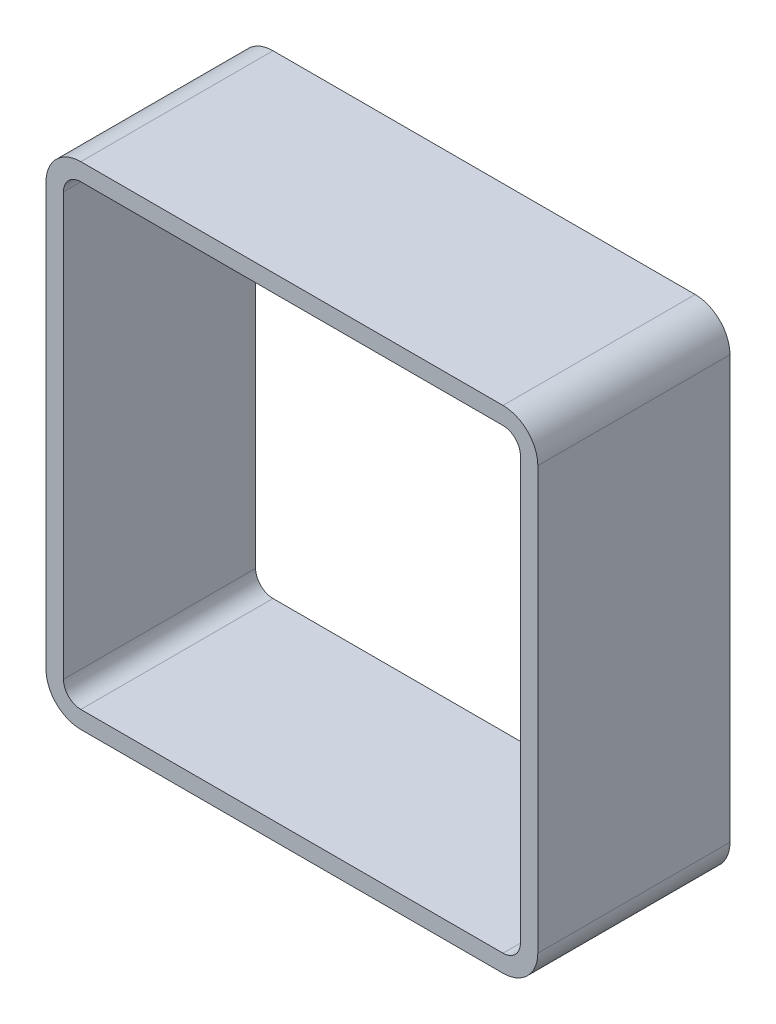
SolidWorks part; units mm, degrees
ref_plane "Front Plane" through (0, 0, 0) normal (0, 0, 1) x (1, 0, 0)
ref_plane "Top Plane" through (0, 0, 0) normal (0, 1, 0) x (1, 0, 0)
ref_plane "Right Plane" through (0, 0, 0) normal (1, 0, 0) x (0, 0, -1)
sketch "Sketch1" plane through (0, 0, 0) normal (0, 0, 1) x (1, 0, 0)
  line L0 (-27.9, 30.2) -> (27.9, 30.2)
  line L1 (-27.9, -32.5) -> (27.9, -32.5)
  line L2 (-32.5, -27.9) -> (-32.5, 27.9)
  line L3 (-27.9, 32.5) -> (27.9, 32.5)
  line L4 (32.5, -27.9) -> (32.5, 27.9)
  line L5 (-32.5, -32.5) -> (32.5, 32.5) construction
  line L6 (-32.5, 32.5) -> (32.5, -32.5) construction
  line L7 (30.2, -27.9) -> (30.2, 27.9)
  line L8 (-27.9, -30.2) -> (27.9, -30.2)
  line L9 (-30.2, -27.9) -> (-30.2, 27.9)
  arc A0 (-32.5, 27.9) -> (-27.9, 32.5) centre (-27.9, 27.9) cw
  arc A1 (27.9, 32.5) -> (32.5, 27.9) centre (27.9, 27.9) cw
  arc A2 (-27.9, -32.5) -> (-32.5, -27.9) centre (-27.9, -27.9) cw
  arc A3 (27.9, -32.5) -> (32.5, -27.9) centre (27.9, -27.9) ccw
  arc A4 (-30.2, 27.9) -> (-27.9, 30.2) centre (-27.9, 27.9) cw
  arc A5 (27.9, 30.2) -> (30.2, 27.9) centre (27.9, 27.9) cw
  arc A6 (27.9, -30.2) -> (30.2, -27.9) centre (27.9, -27.9) ccw
  arc A7 (-27.9, -30.2) -> (-30.2, -27.9) centre (-27.9, -27.9) cw
  point P0 (0, 0)
  dimension "D2" = 4.6
  dimension "Thickness" = 2.3
extrude "BaseSection" add sketch "Sketch1" along normal mid plane 25.4
equation "\"D2@Sketch1\" = \"Thickness@Sketch1\" * (  (IIf(\"Thickness@Sketch1\">3, 1.5, 1))  + 1 ) "
